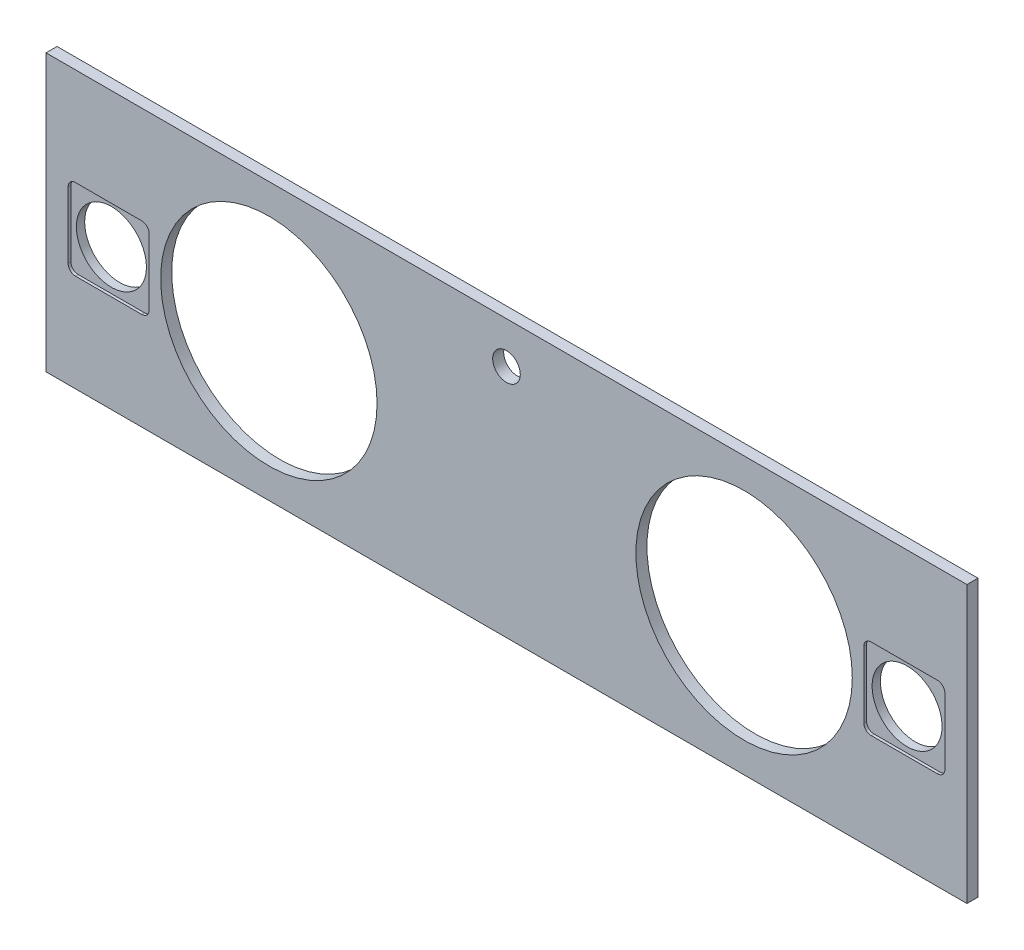
SolidWorks part; units mm, degrees
material "Pine"
ref_plane "Front Plane" through (0, 0, 0) normal (0, 0, 1) x (1, 0, 0)
ref_plane "Top Plane" through (0, 0, 0) normal (0, 1, 0) x (1, 0, 0)
ref_plane "Right Plane" through (0, 0, 0) normal (1, 0, 0) x (0, 0, -1)
sketch "Sketch1" plane through (0, 0, 0) normal (0, 0, 1) x (1, 0, 0)
  line L5 (500, 424.6951) -> (500, -112.2601) construction
  line L6 (0, 0) -> (1000, 0)
  line L10 (0, 0) -> (0, 300)
  line L11 (0, 300) -> (1000, 300)
  line L12 (1000, 0) -> (1000, 300)
  circle A0 centre (242, 150) radius 117.5
  circle A2 centre (758, 150) radius 117.5
  circle A3 centre (68, 150) radius 38
  circle A4 centre (932, 150) radius 38
  dimension "D1" = 235
  dimension "D8" = 76
  dimension "D2" = 1000
  dimension "D3" = 300
  dimension "D4" = 242
  dimension "D5" = 150
  dimension "D6" = 68
  dimension "D7" = 150
  dimension "D9" = 242
extrude "Boss-Extrude1" add sketch "Sketch1" along normal blind 12 contours A2 | A0 | L10 L11 L12 L6 | A3 | A4 region at (758, 150, 0)
sketch "Sketch4" plane through (0, 0, 12) normal (0, 0, 1) x (1, 0, 0)
  line L0 (0, 0) -> (0, 300) construction
  line L1 (32, 194) -> (104, 194)
  line L2 (24, 186) -> (24, 114)
  line L3 (32, 106) -> (104, 106)
  line L4 (112, 186) -> (112, 114)
  line L5 (0, 0) -> (0, 300) construction
  line L6 (0, 300) -> (1000, 300) construction
  line L7 (500, -84.0445) -> (500, 394.2312) construction
  line L8 (968, 106) -> (896, 106)
  line L9 (888, 186) -> (888, 114)
  line L10 (968, 194) -> (896, 194)
  line L11 (976, 186) -> (976, 114)
  arc A0 (104, 194) -> (112, 186) centre (104, 186) cw
  arc A1 (104, 106) -> (112, 114) centre (104, 114) ccw
  arc A2 (24, 114) -> (32, 106) centre (32, 114) ccw
  arc A3 (24, 186) -> (32, 194) centre (32, 186) cw
  arc A4 (896, 106) -> (888, 114) centre (896, 114) cw
  arc A5 (896, 194) -> (888, 186) centre (896, 186) ccw
  arc A6 (976, 114) -> (968, 106) centre (968, 114) cw
  arc A7 (976, 186) -> (968, 194) centre (968, 186) ccw
  point P16 (67.7235, 149.5451)
  dimension "D1" = 8
  dimension "D2" = 88
  dimension "D3" = 88
  dimension "D4" = 24
  dimension "D5" = 106
  dimension "D6" = 500
extrude "Cut-Extrude1" cut sketch "Sketch4" against normal blind 3 contours L2 A2 L3 A1 L4 A0 L1 A3 | L8 A4 L9 A5 L10 A7 L11 A6
sketch "Sketch6" plane through (0, 0, 12) normal (0, 0, 1) x (1, 0, 0)
  line L2 (0, 300) -> (1000, 300) construction
  line L3 (500, 300) -> (500, 241.385) construction
  circle A0 centre (500, 255) radius 15
  dimension "D3" = 30
  dimension "D2" = 45
extrude "Cut-Extrude2" cut sketch "Sketch6" against normal up to surface (12 mm away) up to face at (894, 150, 0)
equation "\"LENGTH\" = 1000mm"
equation "\"D2@Sketch1\"=\"LENGTH\""
equation "\"D6@Sketch4\"=\"LENGTH\"/2"
equation "\"PLY\"= 12mm"
equation "\"D1@Boss-Extrude1\"=\"PLY\""
equation "\"WIDTH\" = 300mm"
equation "\"CENTER_BRACE_LENGTH\" = 393mm"
equation "\"PANEL_WIDTH\"= \"LENGTH\" - \"CENTER_BRACE_LENGTH\" * 2 - \"PLY\" * 4"
equation "\"PANEL_SMALL_HEIGHT\" = 70mm"
